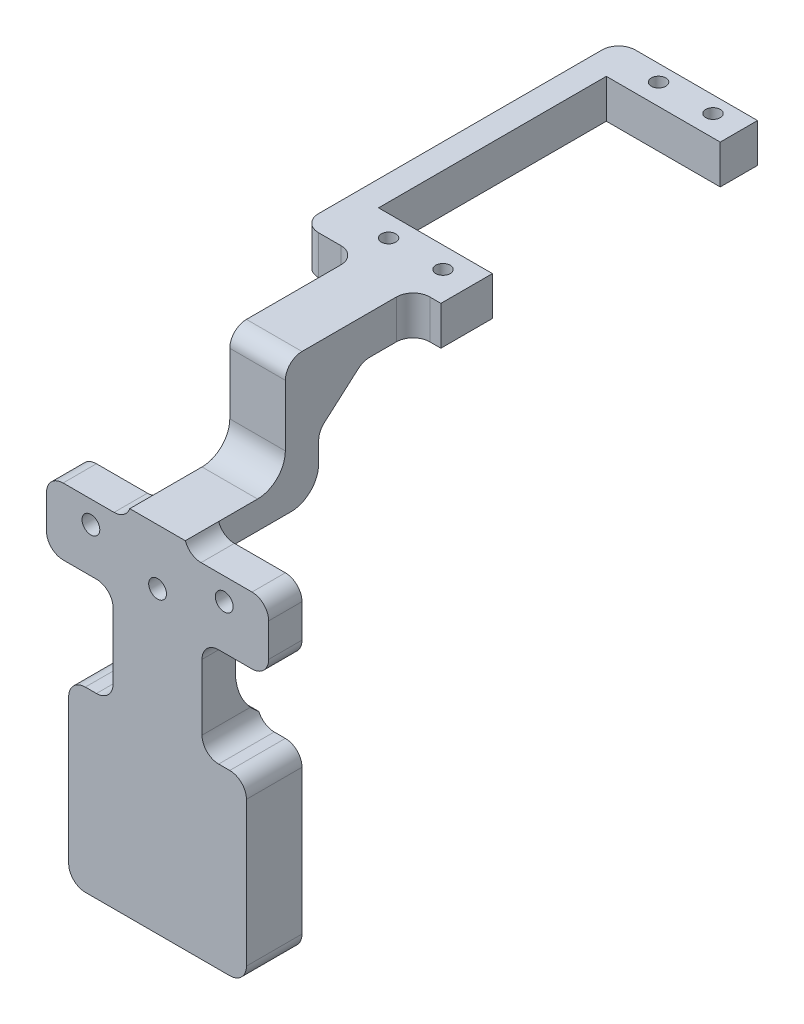
SolidWorks part; units mm, degrees
ref_plane "Front Plane" through (0, 0, 0) normal (0, 0, 1) x (1, 0, 0)
ref_plane "Top Plane" through (0, 0, 0) normal (0, 1, 0) x (1, 0, 0)
ref_plane "Right Plane" through (0, 0, 0) normal (1, 0, 0) x (0, 0, -1)
sketch "Sketch1" plane through (0, 0, 0) normal (0, 0, 1) x (1, 0, 0)
  line L0 (0, 0) -> (0, -151.4897) construction
  line L1 (-13, -85.9078) -> (-8, -85.9078)
  line L2 (-16, -88.9078) -> (-16, -114.9078)
  line L3 (-13, -117.9078) -> (13, -117.9078)
  line L4 (16, -88.9078) -> (16, -114.9078)
  line L6 (0, -101.9078) -> (28.476, -101.9078) construction
  line L9 (-8, -85.9078) -> (-8, -68.0935)
  line L11 (8, -85.9078) -> (8, -68.0935)
  line L12 (8, -85.9078) -> (13, -85.9078)
  line L13 (8, -68.0935) -> (20, -68.0935)
  line L14 (-20, -56.0935) -> (20, -56.0935)
  line L18 (0, -52.2488) -> (-20, -51.3078)
  line L19 (20, -51.3078) -> (0, -52.2488)
  line L20 (20, -68.0935) -> (20, -51.3078)
  line L21 (-20, -68.0935) -> (20, -68.0935)
  line L22 (-20, -51.3078) -> (-20, -68.0935)
  line L25 (20, -68.0935) -> (20, -56.0935)
  line L26 (-20, -68.0935) -> (-8, -68.0935)
  line L27 (-20, -56.0935) -> (-20, -68.0935)
  arc A1 (-16, -114.9078) -> (-13, -117.9078) centre (-13, -114.9078) ccw
  arc A2 (13, -117.9078) -> (16, -114.9078) centre (13, -114.9078) ccw
  arc A3 (13, -85.9078) -> (16, -88.9078) centre (13, -88.9078) cw
  arc A4 (-13, -85.9078) -> (-16, -88.9078) centre (-13, -88.9078) ccw
  point P19 (-16, -117.9078)
  point P22 (16, -117.9078)
  point P25 (16, -85.9078)
  dimension "D1" = 16
  dimension "D5" = 3
  dimension "D2" = 32
  dimension "D3" = 32
  dimension "D4" = 16
  dimension "D6" = 8
  dimension "D7" = 8
  dimension "D8" = 12
  dimension "D9" = 0
extrude "Boss-Extrude1" add sketch "Sketch1" along normal blind 10
sketch "Sketch2" plane through (20, 0, 0) normal (1, 0, 0) x (0, 0, -1)
  line L0 (-4, -56.0935) -> (-4, -75.9441)
  line L1 (-10, -56.0935) -> (0, -56.0935) construction
  line L3 (0, -85.9078) -> (0, -68.0935) construction
  line L4 (-4, -56.0935) -> (0, -56.0935)
  line L5 (0, -56.0935) -> (0, -84.0935)
  arc A0 (0, -84.0935) -> (-4, -75.9441) centre (6.3017, -75.9441) cw
extrude "Cut-Extrude1" cut sketch "Sketch2" against normal up to surface (40 mm away) up to face at (-20, -62.0935, 5)
fillet "Fillet1" radius 3 8 edges at (-8, -68.0935, 7) (-20, -68.0935, 7) (-20, -56.0935, 7) (20, -56.0935, 7) (20, -68.0935, 7) (8, -68.0935, 7) (-8, -85.9078, 5) (8, -85.9078, 5)
sketch "Sketch3" plane through (0, 0, 4) normal (0, 0, -1) x (-1, 0, 0)
  line L0 (-20, -60.0935) -> (20, -60.0935) construction
  line L3 (-20, -59.0935) -> (-20, -65.0935) construction
  line L4 (20, -65.0935) -> (20, -59.0935) construction
  line L5 (17, -56.0935) -> (-17, -56.0935) construction
  line L6 (0, -60.0935) -> (0, -64.0935) construction
  circle A0 centre (-12, -60.0935) radius 1.6
  circle A1 centre (0, -64.0935) radius 1.6
  circle A2 centre (12, -60.0935) radius 1.6
  dimension "D2" = 3.2
  dimension "D3" = 3.2
  dimension "D4" = 12
  dimension "D1" = 4
extrude "Cut-Extrude2" cut sketch "Sketch3" against normal up to surface (6 mm away) up to face at (0, -80.334, 10)
sketch "Sketch4" plane through (0, 0, 0) normal (0, 0, -1) x (-1, 0, 0)
  circle A0 centre (0, -101.9078) radius 16.5 construction
  circle A1 centre (11.6673, -90.2405) radius 1.6 construction
  circle A2 centre (11.6673, -90.2405) radius 1.6
  circle A3 centre (-11.6673, -90.2405) radius 1.6 construction
  circle A4 centre (-11.6673, -90.2405) radius 1.6
  circle A5 centre (-11.6673, -113.575) radius 1.6 construction
  circle A6 centre (-11.6673, -113.575) radius 1.6
  circle A7 centre (11.6673, -113.575) radius 1.6 construction
  circle A8 centre (11.6673, -113.575) radius 1.6
extrude "Cut-Extrude3" cut sketch "Sketch4" against normal blind 7
sketch "Sketch5" plane through (0, 0, 0) normal (1, 0, 0) x (0, 0, -1)
  line L0 (-10, -59.0935) -> (-10, -54.0935)
  line L1 (-10, -51.3078) -> (-10, -68.0935) construction
  line L2 (-10, -54.0935) -> (8, -54.0935)
  line L3 (8, -54.0935) -> (8, -35.0935)
  line L4 (8, -35.0935) -> (88, -35.0935)
  line L5 (88, -35.0935) -> (88, -42.0935)
  line L6 (88, -42.0935) -> (22, -42.0935)
  line L7 (14, -49.0935) -> (14, -59.0935)
  line L8 (14, -59.0935) -> (-10, -59.0935)
  line L9 (14, -49.0935) -> (22, -42.0935)
  dimension "D1" = 5
  dimension "D2" = 6
  dimension "D4" = 7
  dimension "D6" = 80
  dimension "D8" = 7
extrude "Boss-Extrude2" add sketch "Sketch5" along normal mid plane 10
fillet "Fillet2" radius 3 2 edges at (-5, -56.0935, 7) (5, -56.0935, 7)
fillet "Fillet3" radius 2 1 edges at (0, -59.0935, 4)
fillet "Fillet4" radius 5 2 edges at (0, -54.0935, -8) (0, -59.0935, -14)
fillet "Fillet5" radius 3 1 edges at (0, -35.0935, -8)
sketch "Sketch7" plane through (0, -35.0935, 0) normal (0, 1, 0) x (1, 0, 0)
  line L0 (10, 88) -> (10, 51.1645) construction
  line L1 (10, 88) -> (-15, 88)
  line L2 (10, 88) -> (10, 31)
  line L3 (10, 31) -> (-15, 31)
  line L4 (-15, 88) -> (-15, 31)
  line L5 (10, 88) -> (10, 67.3138) construction
  dimension "D1" = 10
extrude "Boss-Extrude3" add sketch "Sketch7" against normal up to surface (7 mm away) up to face at (0, -42.0935, -55)
sketch "Sketch8" plane through (0, -35.0935, 0) normal (0, 1, 0) x (1, 0, 0)
  line L0 (0, 11) -> (0, 88) construction
  line L1 (10.7942, 40.28) -> (10.7942, 81.28)
  line L3 (-5, 11) -> (5, 11) construction
  line L4 (10, 88) -> (-15, 88) construction
  line L6 (-10.5, 81.28) -> (10.7942, 81.28)
  line L7 (-10.5, 81.28) -> (-10.5, 40.28)
  line L8 (-10.5, 40.28) -> (10.7942, 40.28)
  line L10 (-8, 88) -> (8, 88) construction
  line L11 (0, 88) -> (0, 44.5519) construction
  circle A0 centre (-4.9, 85.08) radius 1.3047
  circle A1 centre (4.9, 85.08) radius 1.3047
  circle A2 centre (4.9, 36.48) radius 1.3047
  circle A3 centre (-4.9, 36.48) radius 1.3047
extrude "Cut-Extrude4" cut sketch "Sketch8" against normal up to surface (7 mm away) up to face at (-1.25, -42.0935, -43)
fillet "Fillet6" radius 3 6 edges at (-15, -38.5935, -88) (-15, -38.5935, -31) (-5, -38.5935, -31) (5, -38.5935, -31) (0, -49.0935, -14) (0, -42.0935, -22)
